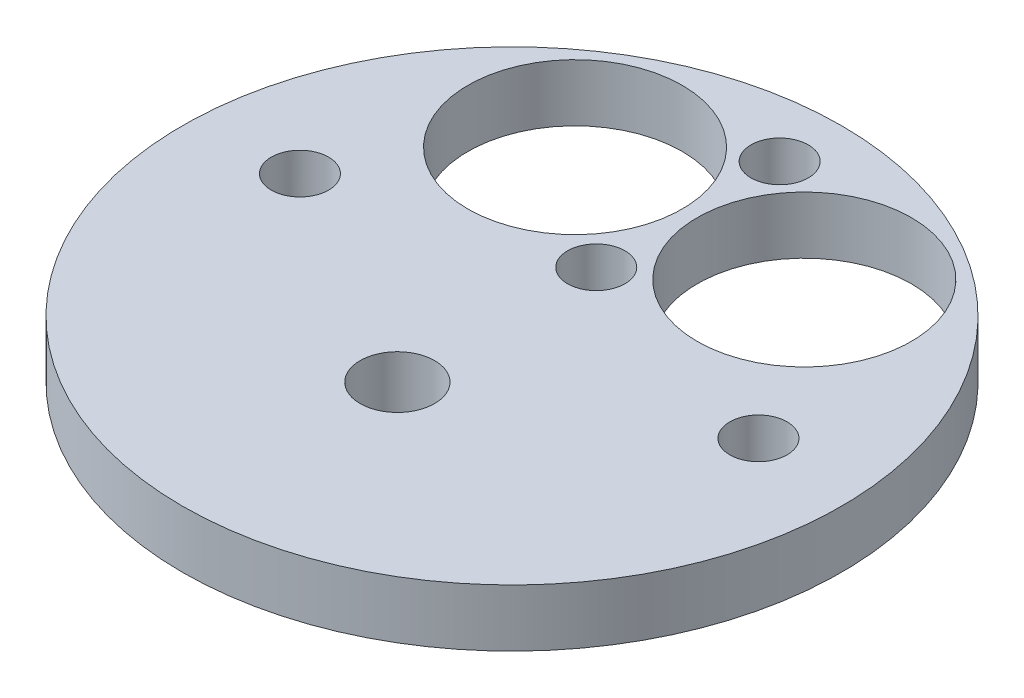
SolidWorks part; units mm, degrees
ref_plane "Front Plane" through (0, 0, 0) normal (0, 0, 1) x (1, 0, 0)
ref_plane "Top Plane" through (0, 0, 0) normal (0, 1, 0) x (1, 0, 0)
ref_plane "Right Plane" through (0, 0, 0) normal (1, 0, 0) x (0, 0, -1)
sketch "Sketch1" plane through (0, 0, 0) normal (0, 1, 0) x (1, 0, 0)
  circle A0 centre (0, 0) radius 36.5125
  dimension "D1" = 73.025
extrude "Boss-Extrude1" add sketch "Sketch1" along normal blind 6.35
sketch "Sketch2" plane through (0, 6.35, 0) normal (0, 1, 0) x (1, 0, 0)
  line L0 (-36.5125, 0) -> (36.5125, 0) construction
  line L1 (0, 36.5125) -> (0, -36.5125) construction
  line L2 (0, 0) -> (25.8182, -25.8182) construction
  line L3 (0, 0) -> (-25.8182, 25.8182) construction
  line L4 (-25.8182, 25.8182) -> (25.8182, 25.8182) construction
  line L5 (25.8182, 25.8182) -> (-25.8182, -25.8182) construction
  line L6 (-25.8182, -25.8182) -> (25.8182, -25.8182) construction
  line L7 (25.8182, -25.8182) -> (25.8182, 25.8182) construction
  line L8 (-25.8182, 25.8182) -> (-25.8182, -25.8182) construction
  circle A0 centre (0, 0) radius 36.5125 construction
sketch "Sketch5" plane through (0, 6.35, 0) normal (0, 1, 0) x (1, 0, 0)
  circle A0 centre (12.7, 15.875) radius 11.8745
  circle A1 centre (-12.7, 15.875) radius 11.8745
sketch "Sketch6" plane through (0, 6.35, 0) normal (0, 1, 0) x (1, 0, 0)
  circle A0 centre (0, 0) radius 36.5125 construction
sketch "Sketch9" plane through (0, 6.35, 0) normal (0, 1, 0) x (1, 0, 0)
  circle A2 centre (0, 26.0223) radius 3.175
  circle A3 centre (0, 5.7277) radius 3.175
sketch "Sketch10" plane through (0, 6.35, 0) normal (0, 1, 0) x (1, 0, 0)
  line L2 (-12.7, 33.655) -> (12.7, 33.655) construction
  line L3 (-12.7, 5.715) -> (12.7, 5.715) construction
  arc A6 (-12.7, 33.655) -> (-12.7, 5.715) centre (-12.7, 19.685) ccw construction
  arc A14 (12.7, 5.715) -> (12.7, 33.655) centre (12.7, 19.685) ccw construction
sketch "Sketch16" plane through (0, 0, 0) normal (0, -1, 0) x (1, 0, 0)
  circle A0 centre (0, 0) radius 36.5125
  dimension "D1" = 73.025
sketch "Sketch18" plane through (0, 6.35, 0) normal (0, 1, 0) x (1, 0, 0)
  line L0 (0, 1.905) -> (25.4, 1.905) construction
  line L1 (0, 36.5125) -> (0, -36.5125) construction
  line L2 (0, 1.905) -> (0, -20.1363) construction
  line L3 (-36.5125, 0) -> (36.5125, 0) construction
  circle A0 centre (25.4, 1.905) radius 3.175
  circle A1 centre (-25.4, 1.905) radius 3.175
  dimension "D1" = 1.905
  dimension "D2" = 25.4
sketch "Sketch19" plane through (0, 6.35, 0) normal (0, 1, 0) x (1, 0, 0)
  line L0 (0, 19.494) -> (0, 29.654) construction
  line L1 (0, 36.5125) -> (0, -36.5125) construction
  line L2 (0, 19.494) -> (0, 9.334) construction
  circle A0 centre (-12.7, 19.685) radius 11.8745
  circle A1 centre (12.7, 19.685) radius 11.8745
  circle A2 centre (0, 29.654) radius 3.175
  circle A3 centre (0, 9.334) radius 3.175
extrude "Cut-Extrude1" cut sketch "Sketch19" against normal blind 16.764
extrude "Cut-Extrude2" cut sketch "Sketch18" against normal blind 16.764
sketch "Sketch20" plane through (0, 6.35, 0) normal (0, 1, 0) x (1, 0, 0)
  circle A0 centre (-25.4, 1.905) radius 8.001 construction
  circle A1 centre (25.4, 1.905) radius 8.001 construction
ref_axis "Axis1" through (0, -3.81, 0) along (0, 1, 0)
sketch "Sketch21" plane through (0, 6.35, 0) normal (0, 1, 0) x (1, 0, 0)
  line L0 (0, 36.5125) -> (0, -36.5125) construction
  circle A0 centre (0, -12.7) radius 4.1275
  dimension "D2" = 8.255
  dimension "D1" = 12.7
extrude "Cut-Extrude3" cut sketch "Sketch21" against normal through all
